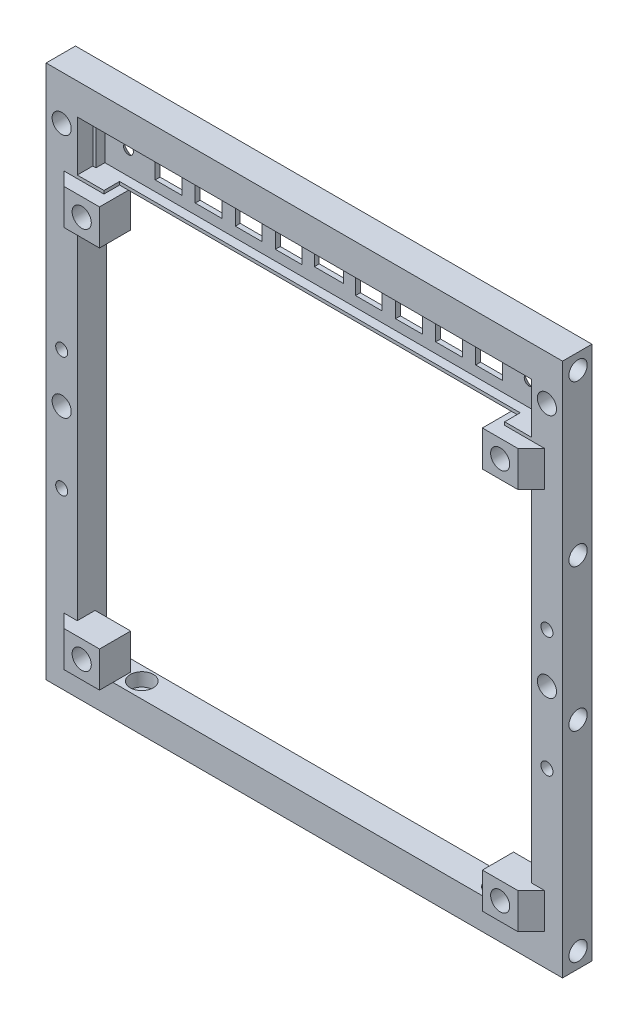
SolidWorks part; units mm, degrees
ref_plane "Front Plane" through (0, 0, 0) normal (0, 0, 1) x (1, 0, 0)
ref_plane "Top Plane" through (0, 0, 0) normal (0, 1, 0) x (1, 0, 0)
ref_plane "Right Plane" through (0, 0, 0) normal (1, 0, 0) x (0, 0, -1)
sketch "Sketch1" plane through (0, 0, 0) normal (0, 0, 1) x (1, 0, 0)
  line L1 (-58, -60) -> (58, -60)
  line L2 (-58, -60) -> (-58, 60)
  line L3 (-58, 60) -> (58, 60)
  line L4 (58, -60) -> (58, 60)
  line L5 (-58, -60) -> (58, 60) construction
  line L6 (-58, 60) -> (58, -60) construction
  line L7 (-51, -53) -> (51, -53)
  line L8 (-51, -53) -> (-51, 53)
  line L9 (-51, 53) -> (51, 53)
  line L10 (51, -53) -> (51, 53)
  line L11 (-51, -53) -> (51, 53) construction
  line L12 (-51, 53) -> (51, -53) construction
  point P0 (0, 0)
  point P6 (0, 0)
  dimension "D1" = 116
  dimension "D2" = 120
  dimension "D3" = 7
  dimension "D4" = 7
extrude "Boss-Extrude1" add sketch "Sketch1" along normal blind 7
sketch "Sketch2" plane through (-58, 0, 0) normal (-1, 0, 0) x (0, 0, 1)
  line L0 (3.5, 56.5) -> (3.5, -56.5) construction
  line L1 (7, 60) -> (0, 60) construction
  circle A0 centre (3.5, -56.5) radius 2.05
  circle A2 centre (3.5, 56.5) radius 2.05
  circle A3 centre (3.5, 20.5) radius 2.05
  circle A4 centre (3.5, -11.5) radius 2.05
  point P2 (3.5, 0)
  point P7 (3.5, 60)
  dimension "D2" = 4.1
  dimension "D3" = 36
  dimension "D4" = 45
  dimension "D1" = 3.5
extrude "Cut-Extrude1" cut sketch "Sketch2" against normal blind 6
mirror "Mirror1" about plane through (0, 0, 0) normal (1, 0, 0) of "Cut-Extrude1"
sketch "Sketch3" plane through (0, -53, 0) normal (0, 1, 0) x (1, 0, 0)
  line L0 (0, 0) -> (0, -7) construction
  line L1 (-51, 0) -> (51, 0) construction
  line L2 (-51, -7) -> (51, -7) construction
  line L3 (40, -3.5) -> (-40, -3.5) construction
  circle A0 centre (40, -3.5) radius 1.35
  circle A1 centre (-40, -3.5) radius 1.35
  point P9 (0, -3.5)
  dimension "D1" = 2.7
  dimension "D2" = 80
extrude "Cut-Extrude2" cut sketch "Sketch3" against normal through all
sketch "Sketch4" plane through (0, -53, 0) normal (0, 1, 0) x (1, 0, 0)
  circle A0 centre (40, -3.5) radius 2.6
  circle A1 centre (-40, -3.5) radius 2.6
  dimension "D1" = 5.2
extrude "Cut-Extrude3" cut sketch "Sketch4" against normal blind 3
sketch "Sketch5" plane through (0, 0, 0) normal (0, 0, -1) x (-1, 0, 0)
  line L0 (-54.5, -60) -> (-54.5, 60) construction
  line L1 (58, -60) -> (-58, -60) construction
  line L2 (-58, 60) -> (58, 60) construction
  line L3 (-51, 0) -> (-58, 0) construction
  line L4 (-51, -53) -> (-51, 53) construction
  line L5 (-58, -60) -> (-58, 60) construction
  line L6 (0, 60) -> (0, -60) construction
  line L7 (51, -53) -> (-51, -53) construction
  circle A0 centre (-54.5, 6) radius 1.35
  circle A1 centre (54.5, 6) radius 1.35
  circle A2 centre (-54.5, -21) radius 1.35
  circle A3 centre (54.5, -21) radius 1.35
  point P12 (-54.5, 0)
  point P13 (-54.5, 0)
  dimension "D1" = 2.7
  dimension "D2" = 6
  dimension "D3" = 32
extrude "Cut-Extrude4" cut sketch "Sketch5" against normal through all
sketch "Sketch6" plane through (0, 0, 0) normal (0, 0, -1) x (-1, 0, 0)
  circle A0 centre (-54.5, 6) radius 2.5
  circle A1 centre (54.5, 6) radius 2.5
  circle A2 centre (-54.5, -21) radius 2.5
  circle A3 centre (54.5, -21) radius 2.5
  dimension "D1" = 5
extrude "Cut-Extrude5" cut sketch "Sketch6" against normal blind 3
sketch "Sketch7" plane through (0, 0, 0) normal (0, 0, -1) x (-1, 0, 0)
  line L0 (-51, 53) -> (-58, 53) construction
  line L1 (-58, -60) -> (-58, 60) construction
  line L2 (-54.5, 50) -> (-54.5, -5) construction
  line L3 (-58, 60) -> (58, 60) construction
  circle A0 centre (-54.5, 50) radius 2.15
  circle A1 centre (-54.5, -5) radius 2.15
  point P8 (-54.5, 53)
  dimension "D1" = 4.3
  dimension "D2" = 10
  dimension "D3" = 55
extrude "Cut-Extrude6" cut sketch "Sketch7" against normal through all
mirror "Mirror2" about plane through (0, 0, 0) normal (1, 0, 0) of "Cut-Extrude6"
sketch "Sketch8" plane through (0, 0, 3) normal (0, 0, -1) x (-1, 0, 0)
  line L2 (-55.85, 3.8958) -> (-55.85, 8.1042)
  line L4 (-53.15, 3.8958) -> (-53.15, 8.1042)
  line L5 (-55.85, 3.8958) -> (-53.15, 8.1042) construction
  line L6 (-55.85, 8.1042) -> (-53.15, 3.8958) construction
  line L8 (-55.85, -23.1042) -> (-55.85, -18.8958)
  line L10 (-53.15, -23.1042) -> (-53.15, -18.8958)
  line L11 (-55.85, -23.1042) -> (-53.15, -18.8958) construction
  line L12 (-55.85, -18.8958) -> (-53.15, -23.1042) construction
  circle A0 centre (-54.5, 6) radius 2.5 construction
  circle A1 centre (-54.5, -21) radius 2.5 construction
  circle A2 centre (-54.5, -21) radius 2.5 construction
  arc A3 (-53.15, 8.1042) -> (-55.85, 8.1042) centre (-54.5, 6) ccw
  arc A4 (-53.15, -18.8958) -> (-55.85, -18.8958) centre (-54.5, -21) ccw
  circle A5 centre (-54.5, 6) radius 1.35 construction
  circle A6 centre (-54.5, -21) radius 1.35 construction
  arc A7 (-55.85, -23.1042) -> (-53.15, -23.1042) centre (-54.5, -21) ccw
  arc A8 (-55.85, 3.8958) -> (-53.15, 3.8958) centre (-54.5, 6) ccw
  point P0 (-54.5, 6)
  point P8 (-54.5, -21)
extrude "Cut-Extrude7" cut sketch "Sketch8" against normal blind 0.2
sketch "Sketch9" plane through (0, 0, 3.2) normal (0, 0, -1) x (-1, 0, 0)
  line L0 (-53.15, 6) -> (-53.15, 8.1042) construction
  line L1 (-55.85, 4.65) -> (-53.15, 4.65)
  line L2 (-55.85, 4.65) -> (-55.85, 7.35)
  line L3 (-55.85, 7.35) -> (-53.15, 7.35)
  line L4 (-53.15, 4.65) -> (-53.15, 7.35)
  line L5 (-55.85, 4.65) -> (-53.15, 7.35) construction
  line L6 (-55.85, 7.35) -> (-53.15, 4.65) construction
  line L7 (-53.15, -23.1042) -> (-53.15, -18.8958) construction
  line L8 (-55.85, -22.35) -> (-53.15, -22.35)
  line L9 (-55.85, -22.35) -> (-55.85, -19.65)
  line L10 (-55.85, -19.65) -> (-53.15, -19.65)
  line L11 (-53.15, -22.35) -> (-53.15, -19.65)
  line L12 (-55.85, -22.35) -> (-53.15, -19.65) construction
  line L13 (-55.85, -19.65) -> (-53.15, -22.35) construction
  arc A0 (-53.15, 6) -> (-55.85, 6) centre (-54.5, 6) ccw construction
  point P0 (-54.5, 6)
  point P8 (-54.5, -21)
extrude "Cut-Extrude8" cut sketch "Sketch9" against normal blind 0.2
mirror "Mirror3" about plane through (0, 0, 0) normal (1, 0, 0) of "Cut-Extrude8", "Cut-Extrude7"
sketch "Sketch10" plane through (0, 0, 7) normal (0, 0, 1) x (1, 0, 0)
  line L0 (51, -53) -> (51, 53) construction
  line L1 (51, -53) -> (45, -53)
  line L2 (51, -53) -> (51, -47)
  line L3 (51, -47) -> (45, -47)
  line L4 (45, -53) -> (45, -47)
  line L5 (51, -23.5) -> (45, -23.5)
  line L6 (51, -23.5) -> (51, -17.5)
  line L7 (51, -17.5) -> (45, -17.5)
  line L8 (45, -23.5) -> (45, -17.5)
  line L9 (-51, -53) -> (51, -53) construction
  dimension "D1" = 6
  dimension "D2" = 35.5
extrude "Boss-Extrude2" add sketch "Sketch10" against normal offset from surface (5.5 mm away) 1.5 up to face at (-52.35, -5, 0)
sketch "Sketch11" plane through (0, 0, 1.5) normal (0, 0, -1) x (-1, 0, 0)
  line L0 (-51, -23.5) -> (-45, -17.5) construction
  line L2 (-51, -53) -> (-45, -47) construction
  circle A0 centre (-48, -20.5) radius 1.65
  circle A1 centre (-48, -50) radius 1.65
  dimension "D1" = 3.3
extrude "Cut-Extrude9" cut sketch "Sketch11" against normal through all
mirror "Mirror4" about plane through (0, 0, 0) normal (1, 0, 0) of "Cut-Extrude9", "Boss-Extrude2"
sketch "Sketch12" plane through (0, 0, 0) normal (0, 0, -1) x (-1, 0, 0)
  line L0 (51, 53) -> (51, -53) construction
  line L1 (-51, 53) -> (51, 53)
  line L2 (-51, 53) -> (-51, 41)
  line L3 (-51, 41) -> (51, 41)
  line L4 (51, 53) -> (51, 41)
  dimension "D1" = 12
extrude "Boss-Extrude3" add sketch "Sketch12" against normal blind 1.5
sketch "Sketch13" plane through (0, 0, 1.5) normal (0, 0, 1) x (1, 0, 0)
  line L0 (-51, 53) -> (51, 41) construction
  line L2 (-50.3, 41.7) -> (50.3, 41.7)
  line L3 (-50.3, 41.7) -> (-50.3, 52.3)
  line L4 (-50.3, 52.3) -> (50.3, 52.3)
  line L5 (50.3, 41.7) -> (50.3, 52.3)
  line L6 (-50.3, 41.7) -> (50.3, 52.3) construction
  line L7 (-50.3, 52.3) -> (50.3, 41.7) construction
  line L8 (-51, 41) -> (51, 41)
  line L9 (-51, 41) -> (-51, 53)
  line L10 (-51, 53) -> (51, 53)
  line L11 (51, 41) -> (51, 53)
  line L12 (-51, 41) -> (51, 53) construction
  line L13 (-51, 53) -> (51, 41) construction
  point P4 (0, 47)
  point P9 (0, 47)
  dimension "D1" = 100.6
  dimension "D2" = 10.6
extrude "Boss-Extrude4" add sketch "Sketch13" along normal blind 2
sketch "Sketch14" plane through (0, 0, 1.5) normal (0, 0, 1) x (1, 0, 0)
  line L0 (0, 52.3) -> (0, 41.7) construction
  line L1 (50.3, 52.3) -> (-50.3, 52.3) construction
  line L2 (-50.3, 41.7) -> (50.3, 41.7) construction
  line L3 (-50.3, 47) -> (50.3, 47) construction
  line L4 (50.3, 41.7) -> (50.3, 52.3) construction
  line L5 (-33, 50) -> (-39, 50)
  line L6 (-3.25, 45) -> (3.25, 45)
  line L7 (-3.25, 45) -> (-3.25, 49)
  line L8 (-3.25, 49) -> (3.25, 49)
  line L9 (3.25, 45) -> (3.25, 49)
  line L10 (-3.25, 45) -> (3.25, 49) construction
  line L11 (-3.25, 49) -> (3.25, 45) construction
  line L12 (6, 44) -> (12, 44)
  line L13 (6, 44) -> (6, 50)
  line L14 (6, 50) -> (12, 50)
  line L15 (12, 44) -> (12, 50)
  line L16 (6, 44) -> (12, 50) construction
  line L17 (6, 50) -> (12, 44) construction
  line L18 (15, 44) -> (21, 44)
  line L19 (15, 44) -> (15, 50)
  line L20 (15, 50) -> (21, 50)
  line L21 (21, 44) -> (21, 50)
  line L22 (15, 44) -> (21, 50) construction
  line L23 (15, 50) -> (21, 44) construction
  line L24 (24, 44) -> (30, 44)
  line L25 (24, 44) -> (24, 50)
  line L26 (24, 50) -> (30, 50)
  line L27 (30, 44) -> (30, 50)
  line L28 (24, 44) -> (30, 50) construction
  line L29 (24, 50) -> (30, 44) construction
  line L30 (33, 44) -> (39, 44)
  line L31 (33, 44) -> (33, 50)
  line L32 (33, 50) -> (39, 50)
  line L33 (39, 44) -> (39, 50)
  line L34 (33, 44) -> (39, 50) construction
  line L35 (33, 50) -> (39, 44) construction
  line L36 (-39, 44) -> (-39, 50)
  line L37 (-33, 44) -> (-39, 44)
  line L38 (-33, 44) -> (-33, 50)
  line L39 (-24, 50) -> (-30, 50)
  line L40 (-30, 44) -> (-30, 50)
  line L41 (-24, 44) -> (-30, 44)
  line L42 (-24, 44) -> (-24, 50)
  line L43 (-15, 50) -> (-21, 50)
  line L44 (-21, 44) -> (-21, 50)
  line L45 (-15, 44) -> (-21, 44)
  line L46 (-15, 44) -> (-15, 50)
  line L47 (-6, 50) -> (-12, 50)
  line L48 (-12, 44) -> (-12, 50)
  line L49 (-6, 44) -> (-12, 44)
  line L50 (-6, 44) -> (-6, 50)
  circle A0 centre (-45, 47) radius 1.3 construction
  circle A1 centre (45, 47) radius 1.3 construction
  point P6 (0, 47)
  point P11 (0, 47)
  point P16 (9, 47)
  point P21 (18, 47)
  point P26 (27, 47)
  point P31 (36, 47)
  dimension "D10" = 2.6
  dimension "D9" = 45
  dimension "D1" = 6.5
  dimension "D2" = 4
  dimension "D3" = 6
  dimension "D4" = 9
  dimension "D5" = 9
  dimension "D6" = 9
  dimension "D7" = 9
  dimension "D8" = 45
extrude "Cut-Extrude10" cut sketch "Sketch14" against normal through all
sketch "Sketch15" plane through (0, 0, 1.5) normal (0, 0, 1) x (1, 0, 0)
  circle A0 centre (-45, 47) radius 1
  circle A1 centre (45, 47) radius 1
  dimension "D1" = 2
extrude "Boss-Extrude5" add sketch "Sketch15" along normal up to surface (2 mm away) up to face at (0, 47, 3.5)
chamfer "Chamfer1" distance 0.4 angle 45 4 edges at (-51, -6, 0) (51, -6, 0) (0, -53, 0) (0, 41, 0)
chamfer "Chamfer2" distance 0.4 angle 45 4 edges at (0, 60, 0) (-58, 0, 0) (0, -60, 0) (58, 0, 0)
chamfer "Chamfer3" distance 0.4 angle 45 36 edges at (-36, 44, 0) (-39, 47, 0) (-36, 50, 0) (-33, 47, 0) (-27, 44, 0) (-30, 47, 0) (-27, 50, 0) (-24, 47, 0) (-18, 44, 0) (-21, 47, 0) (-18, 50, 0) (-15, 47, 0) (-9, 44, 0) (-12, 47, 0) (-9, 50, 0) (-6, 47, 0) (0, 45, 0) (-3.25, 47, 0) (0, 49, 0) (3.25, 47, 0) (9, 44, 0) (6, 47, 0) (9, 50, 0) (12, 47, 0) (18, 44, 0) (15, 47, 0) (18, 50, 0) (21, 47, 0) (36, 44, 0) (33, 47, 0) (36, 50, 0) (39, 47, 0) (27, 44, 0) (24, 47, 0) (27, 50, 0) (30, 47, 0)
sketch "Sketch16" plane through (0, 0, 7) normal (0, 0, 1) x (1, 0, 0)
  line L0 (-45, 41) -> (-45, 41.7)
  line L1 (-51, -17.5) -> (-45, -17.5)
  line L2 (-51, -17.5) -> (-51, -11.5)
  line L3 (-51, -11.5) -> (-45, -11.5)
  line L4 (-45, -17.5) -> (-45, -11.5)
  line L5 (51, -17.5) -> (45, -17.5)
  line L6 (51, -17.5) -> (51, -11.5)
  line L7 (51, -11.5) -> (45, -11.5)
  line L8 (45, -17.5) -> (45, -11.5)
  line L9 (51, 41) -> (45, 41) construction
  line L10 (51, 41) -> (51, 35)
  line L11 (51, 35) -> (45, 35)
  line L12 (45, 41) -> (45, 35)
  line L13 (-51, 41) -> (-45, 41) construction
  line L14 (-51, 41) -> (-51, 35)
  line L15 (-51, 35) -> (-45, 35)
  line L16 (-45, 41) -> (-45, 35)
  line L17 (-50.3, 41.7) -> (50.3, 41.7) construction
  line L18 (-45, 41.7) -> (-51, 41.7)
  line L19 (-51, 53) -> (-51, 41) construction
  line L20 (-51, 41.7) -> (-51, 41)
  line L21 (45, 41) -> (45, 41.7)
  line L22 (45, 41.7) -> (51, 41.7)
  line L23 (51, 41) -> (51, 53) construction
  line L24 (51, 41.7) -> (51, 41)
  dimension "D1" = 6
extrude "Boss-Extrude7" add sketch "Sketch16" against normal offset from surface (5.5 mm away) 1.5 up to face at (-36, 47, 0)
sketch "Sketch17" plane through (0, 0, 1.5) normal (0, 0, -1) x (-1, 0, 0)
  line L0 (-45, 35) -> (45, -11.5) construction
  line L1 (-45, -11.5) -> (-45, -23.5) construction
  line L2 (-48, -14.5) -> (48, -14.5) construction
  line L3 (-48, -14.5) -> (-48, 38) construction
  line L4 (-48, 38) -> (48, 38) construction
  line L5 (48, -14.5) -> (48, 38) construction
  line L6 (-48, -14.5) -> (48, 38) construction
  line L7 (-48, 38) -> (48, -14.5) construction
  line L8 (45, -11.5) -> (51, -11.5) construction
  circle A0 centre (-48, -14.5) radius 1.65
  circle A1 centre (48, -14.5) radius 1.65
  circle A2 centre (48, 38) radius 1.65
  circle A3 centre (-48, 38) radius 1.65
  point P4 (0, 11.75)
  dimension "D3" = 3.3
  dimension "D1" = 3
  dimension "D2" = 3
extrude "Cut-Extrude11" cut sketch "Sketch17" against normal through all
sketch "Sketch18" plane through (0, 0, 1.5) normal (0, 0, 1) x (1, 0, 0)
  circle A0 centre (-45, 47) radius 1.1
  circle A1 centre (45, 47) radius 1.1
  dimension "D1" = 2.2
extrude "Cut-Extrude12" cut sketch "Sketch18" against normal through all both and the other way through all
chamfer "Chamfer4" distance 1.5 angle 45 2 edges at (-43.9, 47, 0) (46.1, 47, 0)
sketch "Sketch19" plane through (0, 0, 1.5) normal (0, 0, -1) x (-1, 0, 0)
  line L1 (-51, -53) -> (51, -53)
  line L2 (-51, -53) -> (-51, 41)
  line L3 (-51, 41) -> (51, 41)
  line L4 (51, -53) -> (51, 41)
extrude "Cut-Extrude13" cut sketch "Sketch19" against normal through all
ref_plane "Plane1" through (0, 0, 3) normal (0, 0, -1) x (-1, 0, 0)
sketch "Sketch20" plane through (0, 0, 3) normal (0, 0, -1) x (-1, 0, 0)
  line L0 (0, 41.4) -> (0, -53.4) construction
  line L1 (-51, 41) -> (-43, 41)
  line L2 (-51, 41) -> (-51, 33)
  line L3 (-51, 33) -> (-43, 33)
  line L4 (-43, 41) -> (-43, 33)
  line L5 (-51, -53) -> (-43, -53)
  line L6 (-51, -53) -> (-51, -45)
  line L7 (-51, -45) -> (-43, -45)
  line L8 (-43, -53) -> (-43, -45)
  line L9 (-51.4, 41.4) -> (51.4, 41.4) construction
  line L10 (51.4, -53.4) -> (-51.4, -53.4) construction
  line L11 (43, -53) -> (43, -45)
  line L12 (51, -45) -> (43, -45)
  line L13 (51, -53) -> (51, -45)
  line L14 (51, -53) -> (43, -53)
  line L15 (43, 41) -> (43, 33)
  line L16 (51, 33) -> (43, 33)
  line L17 (51, 41) -> (51, 33)
  line L18 (51, 41) -> (43, 41)
  dimension "D1" = 8
extrude "Boss-Extrude8" add sketch "Sketch20" against normal blind 7
chamfer "Chamfer5" distance 3 angle 45 4 edges at (51, 37, 7) (51, -49, 7) (-51, -49, 7) (-51, 37, 7)
sketch "Sketch21" plane through (0, 0, 3) normal (0, 0, -1) x (-1, 0, 0)
  line L0 (-51, 33) -> (-43, 41) construction
  line L1 (-51, -45) -> (-43, -53) construction
  line L2 (0, 0) -> (0, 50000) construction
  line L3 (51, -45) -> (43, -53) construction
  line L4 (51, 33) -> (43, 41) construction
  circle A0 centre (-47, 37) radius 2.15
  circle A1 centre (-47, -49) radius 2.15
  circle A2 centre (47, -49) radius 2.15
  circle A3 centre (47, 37) radius 2.15
  dimension "D1" = 4.3
extrude "Cut-Extrude14" cut sketch "Sketch21" against normal through all
chamfer "Chamfer6" distance 0.4 angle 45 4 edges at (44.85, -49, 3) (-44.85, -49, 3) (-44.85, 37, 3) (44.85, 37, 3)
chamfer "Chamfer7" distance 0.4 angle 45 4 edges at (-52.35, 50, 0) (-52.35, -5, 0) (52.35, -5, 0) (52.35, 50, 0)
